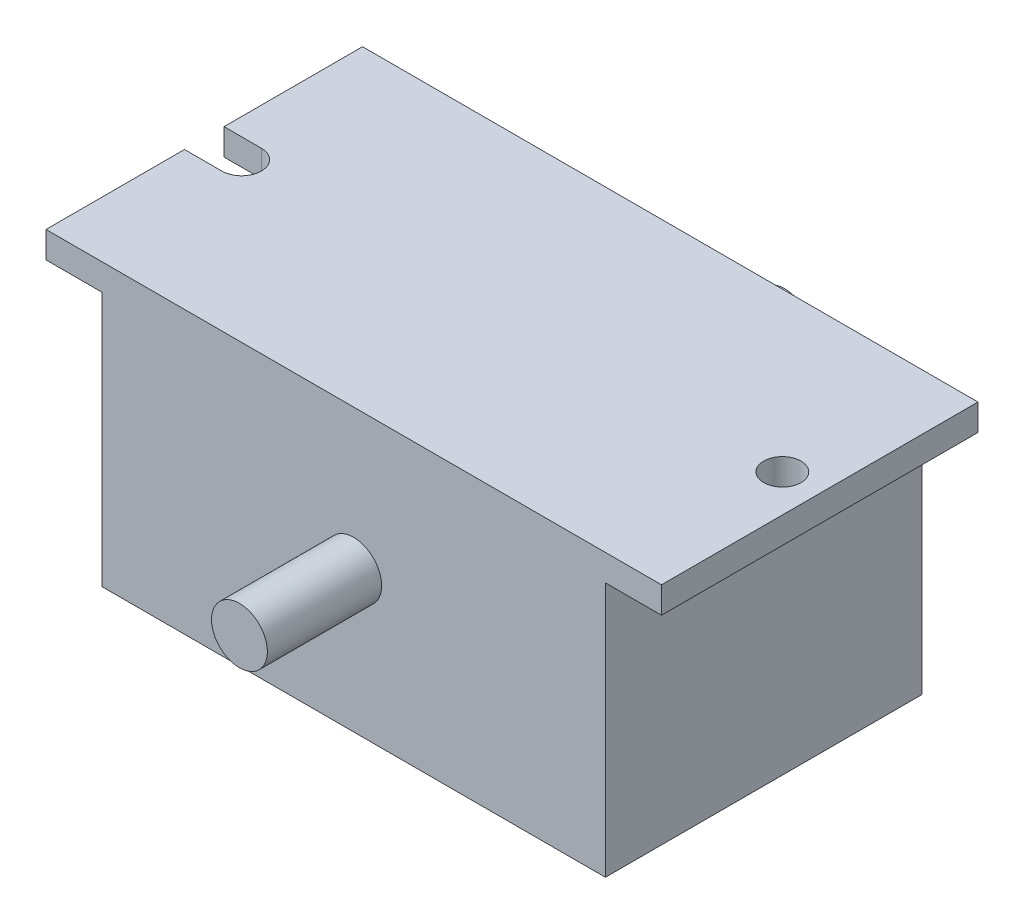
SolidWorks part; units mm, degrees
ref_plane "Front Plane" through (0, 0, 0) normal (0, 0, 1) x (1, 0, 0)
ref_plane "Top Plane" through (0, 0, 0) normal (0, 1, 0) x (1, 0, 0)
ref_plane "Right Plane" through (0, 0, 0) normal (1, 0, 0) x (0, 0, -1)
sketch "Sketch1" plane through (0, 0, 0) normal (0, 0, 1) x (1, 0, 0)
  line L1 (-57.25, 32) -> (57.25, 32)
  line L2 (-57.25, 26) -> (-57.25, -32)
  line L3 (-57.25, -32) -> (57.25, -32)
  line L4 (57.25, 26) -> (57.25, -32)
  line L5 (-57.25, 32) -> (57.25, -32) construction
  line L6 (-57.25, -32) -> (57.25, 32) construction
  line L7 (70, 32) -> (70, 26)
  line L8 (70, 26) -> (57.25, 26)
  line L9 (-57.25, 32) -> (-70, 32)
  line L10 (-70, 32) -> (-70, 26)
  line L11 (-70, 26) -> (-57.25, 26)
  line L12 (57.25, 32) -> (70, 32)
  point P0 (0, 0)
  dimension "D1" = 114.5
  dimension "D2" = 64
  dimension "D3" = 70
  dimension "D4" = 70
  dimension "D5" = 6
  dimension "D6" = 6
  dimension "D7" = 12.75
  dimension "D8" = 114.5
extrude "Boss-Extrude1" add sketch "Sketch1" along normal blind 72
sketch "Sketch2" plane through (0, 32, 0) normal (0, 1, 0) x (1, 0, 0)
  line L0 (-61.5, -31.5) -> (-70, -31.5)
  line L1 (-70, -72) -> (-70, 0) construction
  line L2 (-61.5, -40.5) -> (-70, -40.5)
  line L3 (-70, -31.5) -> (-70, -40.5)
  circle A0 centre (61.5, -36) radius 4.25
  arc A1 (-61.5, -40.5) -> (-61.5, -31.5) centre (-61.5, -36) ccw
  dimension "D3" = 8.5
  dimension "D6" = 9
  dimension "D1" = 61.5
  dimension "D2" = 36
  dimension "D4" = 36
  dimension "D5" = 61.5
extrude "Cut-Extrude1" cut sketch "Sketch2" against normal through all
sketch "Sketch3" plane through (0, 0, 72) normal (0, 0, 1) x (1, 0, 0)
  circle A0 centre (0, 0) radius 6.35
  dimension "D1" = 12.7
extrude "Boss-Extrude2" add sketch "Sketch3" along normal blind 26
sketch "Sketch5" plane through (0, 0, 0) normal (0, 0, -1) x (-1, 0, 0)
  circle A0 centre (0, 0) radius 6.35
  dimension "D1" = 12.7
extrude "Boss-Extrude3" add sketch "Sketch5" along normal blind 26
